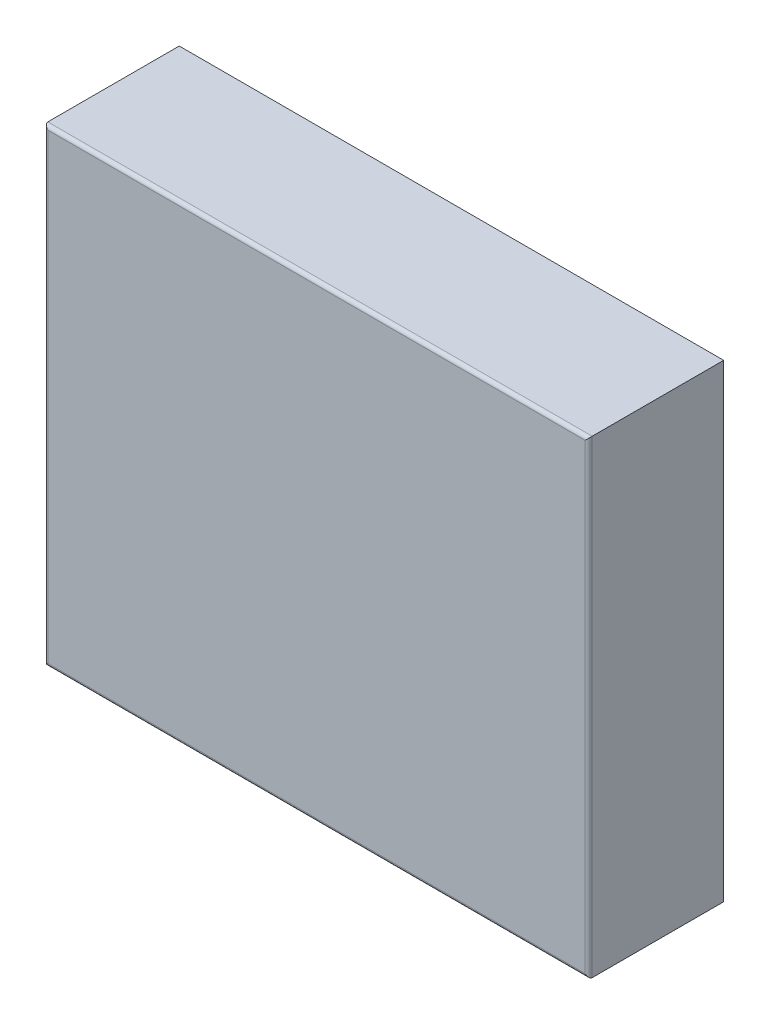
SolidWorks part; units mm, degrees
ref_plane "Płaszczyzna przednia" through (0, 0, 0) normal (0, 0, 1) x (1, 0, 0)
ref_plane "Płaszczyzna górna" through (0, 0, 0) normal (0, 1, 0) x (1, 0, 0)
ref_plane "Płaszczyzna prawa" through (0, 0, 0) normal (1, 0, 0) x (0, 0, -1)
sketch "PCB dim" plane through (0, 0, 0) normal (0, 0, 1) x (1, 0, 0)
  line L1 (-28.75, 24.5) -> (28.75, 24.5)
  line L2 (-28.75, 24.5) -> (-28.75, -24.5)
  line L3 (-28.75, -24.5) -> (28.75, -24.5)
  line L4 (28.75, 24.5) -> (28.75, -24.5)
  point P4 (0, -24.5)
  point P6 (-28.75, 0)
  dimension "D1" = 57.5
  dimension "D2" = 49
sketch "Screw pads" plane through (0, 0, 0) normal (0, 0, 1) x (1, 0, 0)
  line L0 (-28.75, 24.5) -> (28.75, 24.5) construction
  line L1 (-28.75, 24.5) -> (-28.75, -24.5) construction
  line L2 (-28.75, -24.5) -> (28.75, -24.5) construction
  line L3 (28.75, 24.5) -> (28.75, -24.5) construction
  circle A0 centre (-25.25, 21) radius 3
  circle A1 centre (25.25, 21) radius 3
  circle A2 centre (-25.25, -21) radius 3
  circle A3 centre (25.25, -21) radius 3
  dimension "D5" = 6
  dimension "D6" = 6
  dimension "D7" = 6
  dimension "D8" = 6
  dimension "D1" = 3.5
  dimension "D2" = 3.5
  dimension "D3" = 3.5
  dimension "D4" = 3.5
sketch "Screw holes" plane through (0, 0, 0) normal (0, 0, 1) x (1, 0, 0)
  circle A0 centre (-25.25, 21) radius 1.3
  circle A1 centre (25.25, 21) radius 1.3
  circle A2 centre (25.25, -21) radius 1.3
  circle A3 centre (-25.25, -21) radius 1.3
  point P15 (0, 0)
  dimension "D1" = 2.6
  dimension "D2" = 2.6
  dimension "D3" = 2.6
  dimension "D4" = 2.6
sketch "Internal dim" plane through (0, 0, 0) normal (0, 0, 1) x (1, 0, 0)
  line L0 (-28.75, 24.5) -> (-28.75, -24.5) construction
  line L1 (-29.35, 25.1) -> (29.35, 25.1)
  line L2 (-29.35, 25.1) -> (-29.35, -25.1)
  line L3 (-29.35, -25.1) -> (29.35, -25.1)
  line L4 (29.35, 25.1) -> (29.35, -25.1)
  line L5 (28.75, 24.5) -> (28.75, -24.5) construction
  line L6 (-28.75, 24.5) -> (28.75, 24.5) construction
  line L7 (-28.75, -24.5) -> (28.75, -24.5) construction
  dimension "D1" = 0.6
  dimension "D2" = 0.6
  dimension "D3" = 0.6
  dimension "D4" = 0.6
sketch "External dim" plane through (0, 0, 0) normal (0, 0, 1) x (1, 0, 0)
  line L0 (-29.35, 25.1) -> (29.35, 25.1) construction
  line L1 (-30.65, 26.4) -> (30.65, 26.4)
  line L2 (-30.65, 26.4) -> (-30.65, -26.4)
  line L3 (-30.65, -26.4) -> (30.65, -26.4)
  line L4 (30.65, 26.4) -> (30.65, -26.4)
  line L5 (29.35, 25.1) -> (29.35, -25.1) construction
  line L6 (-29.35, 25.1) -> (-29.35, -25.1) construction
  line L7 (-29.35, -25.1) -> (29.35, -25.1) construction
  dimension "D1" = 1.3
  dimension "D2" = 1.3
  dimension "D3" = 1.3
  dimension "D4" = 1.3
extrude "Bottom of case" add sketch "External dim" along normal blind 0.6
extrude "Main body shape" add sketch "External dim<3>" against normal blind 14.6
sketch "External dim<3>" plane through (0, 0, 0) normal (0, 0, 1) x (1, 0, 0) same geometry as "External dim"
extrude "Body case walls" cut sketch "Internal dim" against normal through all
extrude "PCB hold pads" add sketch "Screw pads" against normal blind 5
extrude "Screw holes cut" cut sketch "Screw holes" against normal up to surface (5 mm away) up to face at (28.25, 21, -5)
sketch "Szkic3" plane through (-30.65, 0, 0) normal (-1, 0, 0) x (0, 0, 1)
  line L0 (-5, -18) -> (-5, -24) construction
  line L1 (-10.6, -17) -> (-6.6, -17)
  line L2 (-10.6, -17) -> (-10.6, -7)
  line L3 (-10.6, -7) -> (-6.6, -7)
  line L4 (-6.6, -17) -> (-6.6, -7)
  point P6 (-10.6, -12)
  dimension "D1" = 4
  dimension "D2" = 10
  dimension "D3" = 1.6
  dimension "D4" = 12.5
extrude "USB connector" cut sketch "Szkic3" against normal up to next
sketch "Szkic4" plane through (0, -26.4, 0) normal (0, -1, 0) x (-1, 0, 0)
  line L0 (28.25, 5) -> (22.25, 5) construction
  line L1 (5, 12.6) -> (15, 12.6)
  line L2 (5, 12.6) -> (5, 6.7)
  line L3 (5, 6.7) -> (15, 6.7)
  line L4 (15, 12.6) -> (15, 6.7)
  line L5 (30.65, 14.6) -> (-30.65, 14.6) construction
  dimension "D1" = 13.75
  dimension "D2" = 23.75
  dimension "D3" = 1.7
  dimension "D4" = 2
extrude "LED cutout" cut sketch "Szkic4" against normal up to next
sketch "Szkic5" plane through (-30.65, 0, 0) normal (-1, 0, 0) x (0, 0, 1)
  line L0 (-12.6, -26.4) -> (-12.6, -25.1)
  line L1 (-6.7, -26.4) -> (-6.7, -25.1)
  arc A0 (-12.6, -25.1) -> (-6.7, -25.1) centre (-9.65, -25.5905) cw
  arc A1 (-12.6, -26.4) -> (-6.7, -26.4) centre (-9.65, -26.8905) cw
  point P6 (0, 0)
  point P7 (0, 0)
  point P10 (0, 0)
  point P12 (0, 0)
  point P14 (-9.65, -22.6)
  dimension "D1" = 2.5
extrude "LED curve shape" add sketch "Szkic5" along normal up to surface (-15.65 mm away) from surface up to face at (-15, -25.75, -9.65) starting at face at (-5, -25.75, -9.65)
sketch "Szkic7" plane through (-15, 0, 0) normal (-1, 0, 0) x (0, 0, 1)
  line L0 (-12.6, -25.1) -> (-6.7, -25.1)
  arc A0 (-12.6, -25.1) -> (-6.7, -25.1) centre (-9.65, -25.5905) cw
  arc A1 (-6.7, -25.1) -> (-12.6, -25.1) centre (-9.65, -25.5905) ccw construction
extrude "LED wall 1" add sketch "Szkic7" along normal blind 1.3
extrude "LED wall 2" add sketch "Szkic7<2>" against normal blind 1.2 from surface starting at face at (-5, -24.175, -9.65)
sketch "Szkic7<2>" plane through (-15, 0, 0) normal (-1, 0, 0) x (0, 0, 1) same geometry as "Szkic7"
fillet "Inside bottom rounding" radius 1 8 edges at (0, -25.1, 0) (29.35, 0, 0) (0, 25.1, 0) (-29.35, 0, 0) (-22.25, 21, 0) (28.25, 21, 0) (-22.25, -21, 0) (28.25, -21, 0)
fillet "Outside bottom rounding" radius 0.4 4 edges at (0, 26.4, 0.6) (30.65, 0, 0.6) (0, -26.4, 0.6) (-30.65, 0, 0.6)
fillet "Inside wall rounding" radius 1 12 edges at (-29.0571, -24.8071, -0.2929) (-29.0571, 24.8071, -0.2929) (29.0571, -24.8071, -0.2929) (29.0571, 24.8071, -0.2929) (-10.05, -25.1, -6.7) (-10.05, -25.1, -12.6) (-16.3, -25.1, -9.65) (-3.8, -25.1, -9.65) (-29.35, -25.1, -7.8) (-29.35, 25.1, -7.8) (29.35, -25.1, -7.8) (29.35, 25.1, -7.8)
fillet "LED round 1" radius 1 2 edges at (-10, -26.4, -6.7) (-10, -26.4, -12.6)
fillet "LED round 2" radius 1 10 edges at (-3.3597, -24.9287, -12.792) (-3.3597, -24.9287, -6.508) (-16.7403, -24.9287, -6.508) (-16.7403, -24.9287, -12.792) (-3.8, -22.6, -9.65) (-16.3, -22.6, -9.65)
fillet "LED round 3" radius 1 2 edges at (-15, -26.4, -9.65) (-5, -26.4, -9.65)
equation "\"Screw_offset\"=3.5"
equation "\"D1@Screw pads\" = \"Screw_offset\""
equation "\"D2@Screw pads\" = \"Screw_offset\""
equation "\"D3@Screw pads\" = \"Screw_offset\""
equation "\"D4@Screw pads\" = \"Screw_offset\""
equation "\"Screw_pad_size\"=6"
equation "\"D5@Screw pads\" = \"Screw_pad_size\""
equation "\"Screw_hole_size\"=2.6"
equation "\"D1@Screw holes\" = \"Screw_hole_size\""
equation "\"D3@Screw holes\" = \"Screw_hole_size\""
equation "\"D4@Screw holes\" = \"Screw_hole_size\""
equation "\"WallThickness\"=1.3"
equation "\"D1@External dim\" = \"WallThickness\""
equation "\"D2@External dim\" = \"WallThickness\""
equation "\"D3@External dim\" = \"WallThickness\""
equation "\"D4@External dim\" = \"WallThickness\""
equation "\"D2@Screw holes\"=\"Screw_hole_size\""
equation "\"D1@LED wall 1\"=\"WallThickness\""
